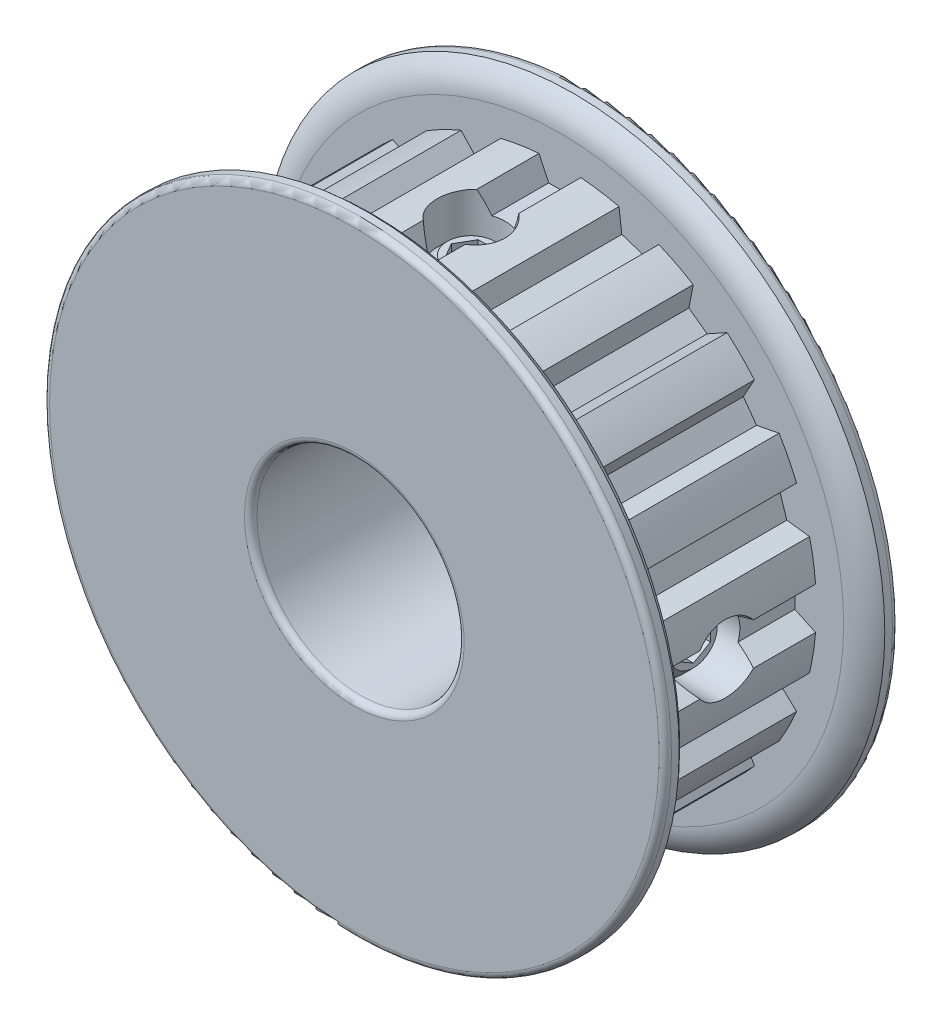
SolidWorks part; units mm, degrees
note: '?' marks a value the reader was unsure of.
ref_plane "Front Plane" through (0, 0, 0) normal (0, 0, 1) x (1, 0, 0)
ref_plane "Top Plane" through (0, 0, 0) normal (0, 1, 0) x (1, 0, 0)
ref_plane "Right Plane" through (0, 0, 0) normal (1, 0, 0) x (0, 0, -1)
sketch "Sketch1" plane through (0, 0, 0) normal (0, 0, 1) x (1, 0, 0)
  line L0 (-1.2827, 15.6591) -> (-0.6905, 14.3891)
  line L1 (-0.6905, 14.3891) -> (0.6905, 14.3891)
  line L2 (0.6905, 14.3891) -> (1.2827, 15.6591)
  line L3 (-1.2827, 15.6591) -> (1.2827, 15.6591)
  line L4 (0, 0) -> (0, 14.3891) construction
  line L5 (0, 14.3891) -> (0, 16.6751) construction
  circle A0 centre (0, 0) radius 16.1671 construction
  circle A1 centre (0, 0) radius 19.05 construction
  circle A2 centre (0, 0) radius 15.7115 construction
  point P6 (0, 15.6591)
  point P11 (0, 16.1671)
  point P13 (0, 19.05)
  point P14 (0, 15.7115)
  dimension "D1" = 1.016
  dimension "PD" = 32.3342
  dimension "D2" = 0.508
  dimension "OD" = 38.1
  dimension "b" = 50
  dimension "bt" = 2.5654
  dimension "ht" = 1.27
  dimension "hs" = 2.286
sketch "Sketch2" plane through (0, 0, 0) normal (1, 0, 0) x (0, 0, -1)
  line L0 (-7.1501, 6.35) -> (7.1501, 6.35)
  line L3 (-7.1501, 6.35) -> (-7.1501, 19.05)
  line L4 (-7.1501, 19.05) -> (-5.4483, 19.05) construction
  line L5 (-5.4483, 19.05) -> (-5.4483, 15.7115) construction
  line L6 (-5.4483, 15.7115) -> (5.4483, 15.7115)
  line L7 (5.4483, 15.7115) -> (5.4483, 19.05) construction
  line L8 (5.4483, 19.05) -> (7.1501, 19.05) construction
  line L9 (7.1501, 19.05) -> (7.1501, 6.35)
  line L10 (-7.1501, 0) -> (7.1501, 0) construction
  line L13 (-7.1501, 19.05) -> (-6.2992, 19.05)
  line L14 (-5.4483, 17.3808) -> (-5.4483, 15.7115)
  line L15 (5.4483, 15.7115) -> (5.4483, 17.3808)
  line L16 (6.2992, 19.05) -> (7.1501, 19.05)
  arc A0 (-5.4483, 17.3808) -> (-6.2992, 19.05) centre (-7.511, 17.3808) ccw
  arc A1 (5.4483, 17.3808) -> (6.2992, 19.05) centre (7.511, 17.3808) cw
  point P12 (-5.4483, 17.3808)
  point P14 (-6.2992, 19.05)
  point P20 (5.4483, 17.3808)
  point P21 (6.2992, 19.05)
  point P25 (5.4483, 0)
  point P26 (-5.4483, 0)
  dimension "OA" = 14.3002
  dimension "Bore" = 12.7
  dimension "Outside Width" = 14.3002
  dimension "Inside Width" = 10.8966
revolve "Revolve1" add sketch "Sketch2" angle 360 mid plane about L10
sketch "Sketch3" plane through (0, 0, 0) normal (0, 0, 1) x (1, 0, 0)
  line L0 (-0.6905, 14.3891) -> (0.6905, 14.3891) construction
  line L1 (0.6905, 14.3891) -> (1.2827, 15.6591) construction
  line L2 (-1.2827, 15.6591) -> (-0.6905, 14.3891) construction
  line L3 (-0.6905, 14.3891) -> (0.6905, 14.3891)
  line L4 (0.6905, 14.3891) -> (1.2827, 15.6591)
  line L5 (-1.2827, 15.6591) -> (-0.6905, 14.3891)
  circle A0 centre (0, 0) radius 15.7115 construction
  arc A1 (1.2827, 15.6591) -> (-1.2827, 15.6591) centre (0, 0) ccw
extrude "Cut-Extrude1" cut sketch "Sketch3" against normal up to vertex (5.4483 mm away) from vertex at 5.4483 starting at point (0, 15.7115, 5.4483)
pattern_circular "CirPattern1" count 20 over 360 about axis through (0, 0, 0) along (0, 0, 1) of "Cut-Extrude1"
fillet "Fillet1" radius 0.381 4 edges at (6.35, 0, -7.1501) (19.05, 0, -7.1501) (19.05, 0, 7.1501) (6.35, 0, 7.1501)
sketch "Sketch5" plane through (0, 0, 0) normal (0, 1, 0) x (1, 0, 0)
  line L1 (1.2827, 0) -> (-1.2827, 0) construction
  line L2 (1.2827, 5.4483) -> (1.2827, -5.4483) construction
  line L3 (-1.2827, 5.4483) -> (-1.2827, -5.4483) construction
  circle A0 centre (0, 0) radius 2.0828
extrude "Cut-Extrude2" cut sketch "Sketch5" along normal through all
sketch "Sketch6" plane through (0, 0, 0) normal (1, 0, 0) x (0, 0, -1)
  line L0 (0, 13.6271) -> (0, 7.112)
  line L1 (6.7691, 6.35) -> (-6.7691, 6.35) construction
  line L3 (2.0828, 14.3891) -> (-2.0828, 14.3891) construction
  line L4 (-1.965, 14.3891) -> (-2.0828, 14.3891) construction
  line L5 (2.0828, 14.3891) -> (1.965, 14.3891) construction
  line L6 (0, 13.6271) -> (-1.458, 13.6271)
  line L7 (-1.458, 13.6271) -> (-2.0828, 13.0023)
  line L8 (-2.0828, 13.0023) -> (-2.0828, 7.7368)
  line L9 (-2.0828, 7.7368) -> (-1.458, 7.112)
  line L10 (-1.458, 7.112) -> (0, 7.112)
  point P12 (0, 6.35)
  point P19 (0, 14.3891)
  dimension "D1" = 0.762
  dimension "D2" = 0.762
  dimension "D3" = 135
  dimension "D4" = 0.6248
revolve "Revolve2" add sketch "Sketch6" angle 360 about L0
sketch "Sketch7" plane through (0, 13.6271, 0) normal (0, 1, 0) x (1, 0, 0)
  line L1 (1.2025, 0) -> (0.6013, 1.0414)
  line L2 (0.6013, 1.0414) -> (-0.6013, 1.0414)
  line L3 (-0.6013, 1.0414) -> (-1.2025, 0)
  line L4 (-1.2025, 0) -> (-0.6013, -1.0414)
  line L5 (-0.6013, -1.0414) -> (0.6013, -1.0414)
  line L6 (0.6013, -1.0414) -> (1.2025, 0)
  circle A0 centre (0, 0) radius 1.0414 construction
  dimension "D1" = 2.0828
extrude "Cut-Extrude3" cut sketch "Sketch7" against normal blind 1.0414
pattern_circular "CirPattern2" count 2 over 270 about axis through (0, 0, 0) along (0, 0, 1) of "Cut-Extrude2", "Revolve2", "Cut-Extrude3"
ref_axis "Center Axis 1" through (0, 0, -6.7691) along (0, 0, 1)?
ref_plane "Contact Plane 1" through (0, 0, 7.1501) normal (0, 0, 1) x (1, 0, 0)
ref_plane "Contact Plane 2" through (0, 0, -7.1501) normal (0, 0, -1) x (-1, 0, 0)
equation "\"D4@Sketch6\" = \"Set Screw Dia@Sketch5\" * .15"
equation "\"D1@Sketch7\" = \"Set Screw Dia@Sketch5\" / 2"
equation "\"D1@Cut-Extrude3\" = \"Set Screw Dia@Sketch5\" / 4"
